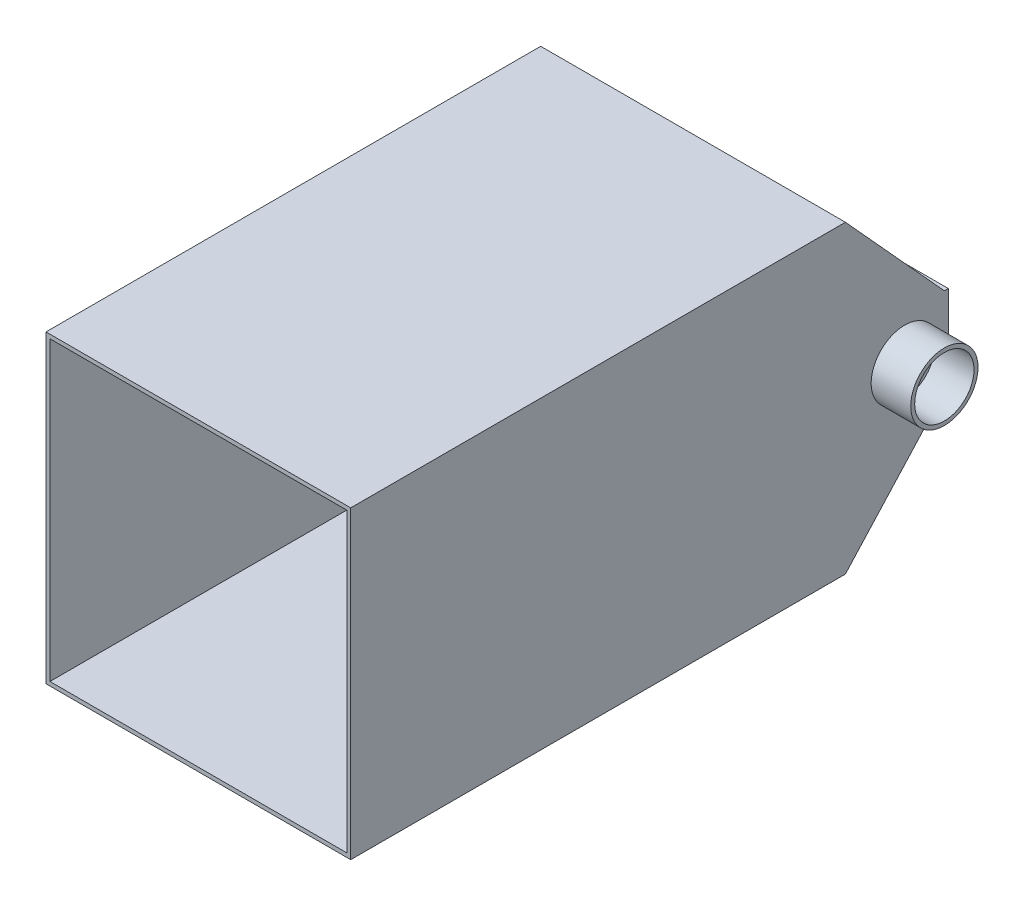
SolidWorks part; units mm, degrees
material "Cast Alloy Steel"
ref_plane "Front Plane" through (0, 0, 0) normal (0, 0, 1) x (1, 0, 0)
ref_plane "Top Plane" through (0, 0, 0) normal (0, 1, 0) x (1, 0, 0)
ref_plane "Right Plane" through (0, 0, 0) normal (1, 0, 0) x (0, 0, -1)
sketch "Sketch1" plane through (0, 0, 0) normal (0, 0, 1) x (1, 0, 0)
  line L0 (-77, 77) -> (77, 77)
  line L1 (-75, 75) -> (75, 75)
  line L2 (-75, 75) -> (-75, -75)
  line L3 (-75, -75) -> (75, -75)
  line L4 (75, 75) -> (75, -75)
  line L5 (-75, 75) -> (75, -75) construction
  line L6 (-75, -75) -> (75, 75) construction
  line L7 (77, 77) -> (77, -77)
  line L8 (-77, -77) -> (77, -77)
  line L9 (-77, 77) -> (-77, -77)
  point P0 (0, 0)
  dimension "D1" = 150
  dimension "D2" = 2
extrude "Boss-Extrude1" add sketch "Sketch1" along normal blind 250
ref_plane "Plane1" through (0, 0, -50) normal (0, 0, -1) x (-1, 0, 0)
sketch "Sketch2" plane through (0, 0, 0) normal (0, 0, -1) x (-1, 0, 0)
  line L1 (-77, 77) -> (77, 77)
  line L2 (-77, 77) -> (-77, -77)
  line L3 (-77, -77) -> (77, -77)
  line L4 (77, 77) -> (77, -77)
  line L5 (75, -75) -> (-75, -75)
  line L6 (75, -75) -> (75, 75)
  line L7 (75, 75) -> (-75, 75)
  line L8 (-75, -75) -> (-75, 75)
sketch "Sketch3" plane through (0, 0, -50) normal (0, 0, -1) x (-1, 0, 0)
  line L0 (-77, 77) -> (-77, -77) construction
  line L1 (-77, 22) -> (77, 22)
  line L2 (-77, 22) -> (-77, -22)
  line L3 (-77, -22) -> (77, -22)
  line L4 (77, 22) -> (77, -22)
  line L5 (77, 77) -> (77, -77) construction
  line L6 (-25, 0) -> (75, 0) construction
  line L9 (-75, 20) -> (75, 20)
  line L10 (75, -75) -> (75, 75) construction
  line L15 (0, 17) -> (0, -17) construction
  line L16 (75, 20) -> (75, -20)
  line L17 (-75, -20) -> (75, -20)
  line L18 (-75, 20) -> (-75, -20)
  point P14 (-77, 0)
  dimension "D1" = 22
  dimension "D2" = 2
loft "Loft1" add section "Sketch2" section "Sketch3" connector at (77, -77, 0) connector at (77, -22, -50)
loft "Cut-Loft1" cut section "Sketch2<3>" section "Sketch3<4>" connector at (75, 75, 0) connector at (75, 20, -50)
sketch "Sketch2<3>" plane through (0, 0, 0) normal (0, 0, -1) x (-1, 0, 0) same geometry as "Sketch2"
sketch "Sketch3<4>" plane through (0, 0, -50) normal (0, 0, -1) x (-1, 0, 0) same geometry as "Sketch3"
sketch "Sketch4" plane through (-77, 0, 0) normal (-1, 0, 0) x (0, 0, 1)
  line L0 (0, 77) -> (0, -77) construction
  line L1 (0, 0) -> (-50, 0) construction
  line L2 (-50, 22) -> (-50, -22) construction
  circle A0 centre (-30, 0) radius 4
  dimension "D1" = 8
  dimension "D2" = 30
extrude "Cut-Extrude1" cut sketch "Sketch4" against normal through all both and the other way through all
sketch "Sketch5" plane through (77, 0, 0) normal (1, 0, 0) x (0, 0, -1)
  circle A0 centre (30, 0) radius 15
  circle A1 centre (30, 0) radius 17
  dimension "D1" = 30
  dimension "D2" = 2
extrude "Boss-Extrude2" add sketch "Sketch5" along normal blind 20
extrude "Boss-Extrude3" add sketch "Sketch5<2>" against normal blind 20 from surface starting at face at (-77, 4, -30)
sketch "Sketch5<2>" plane through (77, 0, 0) normal (1, 0, 0) x (0, 0, -1) same geometry as "Sketch5"
sketch "Sketch6" plane through (0, 0, -50) normal (0, 0, -1) x (-1, 0, 0)
  line L0 (-77, -22) -> (77, -22) construction
  line L1 (-77, 22) -> (-37, 22)
  line L2 (-77, 22) -> (-77, -22)
  line L3 (-77, -22) -> (-37, -22)
  line L4 (-37, 22) -> (-37, -22)
  line L6 (77, 22) -> (27, 22)
  line L7 (77, 22) -> (77, -22)
  line L8 (77, -22) -> (27, -22)
  line L9 (27, 22) -> (27, -22)
  dimension "D1" = 40
  dimension "D2" = 50
extrude "Boss-Extrude4" add sketch "Sketch6" along normal blind 2
